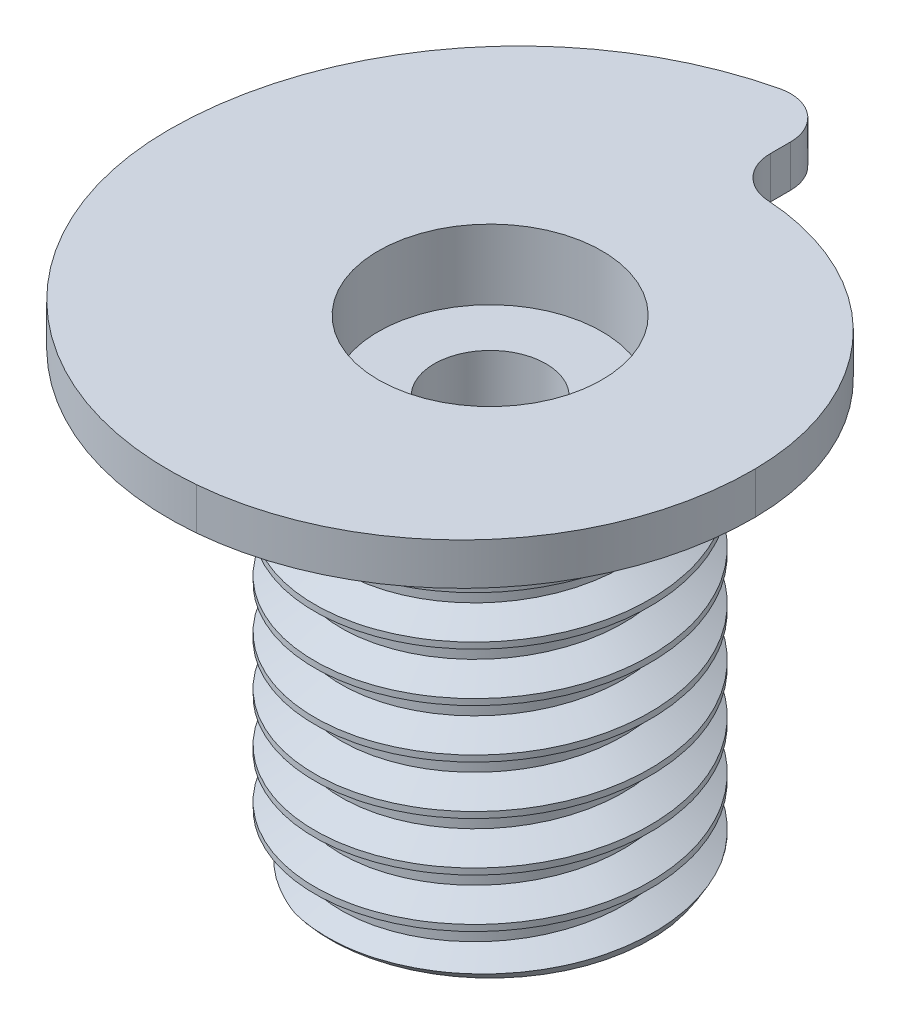
SolidWorks part; units mm, degrees
ref_plane "Front Plane" through (0, 0, 0) normal (0, 0, 1) x (1, 0, 0)
ref_plane "Top Plane" through (0, 0, 0) normal (0, 1, 0) x (1, 0, 0)
ref_plane "Right Plane" through (0, 0, 0) normal (1, 0, 0) x (0, 0, -1)
sketch "Sketch1" plane through (0, 0, 0) normal (1, 0, 0) x (0, 0, -1)
  line L4 (12, 30) -> (12, 0)
  line L6 (0, 0) -> (0, 30) construction
  line L7 (12, 30) -> (4, 30)
  line L10 (4, 30) -> (4, 5)
  line L11 (4, 5) -> (8, 5)
  line L12 (8, 5) -> (8, 0)
  line L13 (8, 0) -> (12, 0)
  dimension "D1" = 8
  dimension "D2" = 8
  dimension "D3" = 5
  dimension "D6" = 30
  dimension "D7" = 12
revolve "Revolve1" add sketch "Sketch1" angle 360 about L6
chamfer "Chamfer1" distance 1 angle 30 1 edges at (0, 0, -12) first distance on face at (0, 30, -12)
thread "Thread1" pitch 3.5 method cut profile "Thread Profile1" start angle 0, offset 0, length 48, pitch 3.5, diameter 24
ref_plane "Plane1" through (-12, 30, 0) normal (0, 0, 1) x (-1, 0, 0)
sketch "Thread Profile1" plane through (-12, 30, 0) normal (0, 0, 1) x (-1, 0, 0)
  line L0 (0, 0) -> (0, 3.5) construction
  line L11 (0, 0) -> (0, 3.0625)
  line L12 (0, 3.0625) -> (-1.8944, 1.9687)
  line L13 (-1.8944, 1.9687) -> (-1.8944, 1.0937)
  line L15 (-1.8944, 1.0937) -> (0, 0)
  line L17 (-1.8944, 1.5312) -> (0, 1.5312) construction
  point P2 (0, 0)
  dimension "Pitch" = 3.5
  dimension "Profile_Angle" = 60
  dimension "Profile_Land" = 0.875
  dimension "Profile_Height" = 1.8944
sketch "Sketch2" plane through (0, 30, 0) normal (0, 1, 0) x (1, 0, 0)
  line L1 (0, 11.547) -> (-10, -5.7735) construction
  line L2 (-10, -5.7735) -> (10, -5.7735) construction
  line L3 (10, -5.7735) -> (0, 11.547) construction
  circle A0 centre (0, 0) radius 5.7735 construction
  circle A1 centre (0, 11.547) radius 1.5
  circle A2 centre (10, -5.7735) radius 1.5
  circle A3 centre (-10, -5.7735) radius 1.5
  dimension "D2" = 3
  dimension "D1" = 20
extrude "Cut-Extrude1" [suppressed] cut sketch "Sketch2" against normal blind 4
sketch "Sketch3" plane through (0, 30, 0) normal (0, 1, 0) x (1, 0, 0)
  line L0 (0, 25) -> (0, -25) construction
  line L1 (-25, 0) -> (25, 0) construction
  line L2 (0, 25) -> (0, 17)
  circle A1 centre (0, 0) radius 17 construction
  circle A2 centre (0, 0) radius 19 construction
  circle A3 centre (0, 0) radius 21 construction
  circle A4 centre (0, 0) radius 23 construction
  circle A5 centre (0, 0) radius 25 construction
  arc A6 (0, 25) -> (-23, 0) centre (2.087, 0) ccw
  arc A7 (-23, 0) -> (0, -21) centre (-1.913, 0) ccw
  arc A8 (0, -21) -> (19, 0) centre (-1.8958, -0.1895) ccw
  arc A9 (19, 0) -> (0, 17) centre (1.7548, -0.1564) ccw
  dimension "D1" = 34
  dimension "D2" = 2
  dimension "D3" = 2
  dimension "D4" = 2
  dimension "D5" = 2
extrude "Boss-Extrude1" add sketch "Sketch3" along normal blind 3
sketch "Sketch4" plane through (0, 33, 0) normal (0, 1, 0) x (1, 0, 0)
  circle A2 centre (0, 0) radius 8
  dimension "D1" = 16
extrude "Cut-Extrude2" cut sketch "Sketch4" against normal blind 5
fillet "Fillet1" radius 3 2 edges at (0, 31.5, -17) (0, 31.5, -25)
sketch "Sketch5" plane through (0, 33, 0) normal (0, 1, 0) x (1, 0, 0)
  arc A0 (-6.606, 16.744) -> (-18, 0) centre (0, 0) ccw construction
  arc A1 (-7.5235, 19.0695) -> (-20.5, 0) centre (0, 0) ccw
  arc A2 (-5.6885, 14.4184) -> (-15.5, 0) centre (0, 0) ccw
  arc A3 (-5.6885, 14.4184) -> (-7.5235, 19.0695) centre (-6.606, 16.744) ccw
  arc A4 (-20.5, 0) -> (-15.5, 0) centre (-18, 0) ccw
  arc A5 (-8.6169, -12.278) -> (8.6169, -12.278) centre (0, 0) ccw construction
  arc A6 (-9.7658, -13.9151) -> (9.7658, -13.9151) centre (0, 0) ccw
  arc A7 (-7.4679, -10.6409) -> (7.4679, -10.6409) centre (0, 0) ccw
  arc A8 (-7.4679, -10.6409) -> (-9.7658, -13.9151) centre (-8.6169, -12.278) ccw
  arc A9 (9.7658, -13.9151) -> (7.4679, -10.6409) centre (8.6169, -12.278) ccw
  arc A10 (13.9041, 1.6355) -> (6.0016, 12.6484) centre (0, 0) ccw construction
  arc A11 (15.3939, 1.8107) -> (6.6446, 14.0035) centre (0, 0) ccw
  arc A12 (12.4144, 1.4603) -> (5.3586, 11.2932) centre (0, 0) ccw
  arc A13 (12.4144, 1.4603) -> (15.3939, 1.8107) centre (13.9041, 1.6355) ccw
  arc A14 (6.6446, 14.0035) -> (5.3586, 11.2932) centre (6.0016, 12.6484) ccw
  point P4 (-14.8813, 10.1265)
  point P9 (0, -15)
  point P18 (11.3745, 8.1621)
  dimension "D1" = 18
  dimension "D2" = 2.5
  dimension "D3" = 15
  dimension "D4" = 2
  dimension "D5" = 14
  dimension "D6" = 1.5
